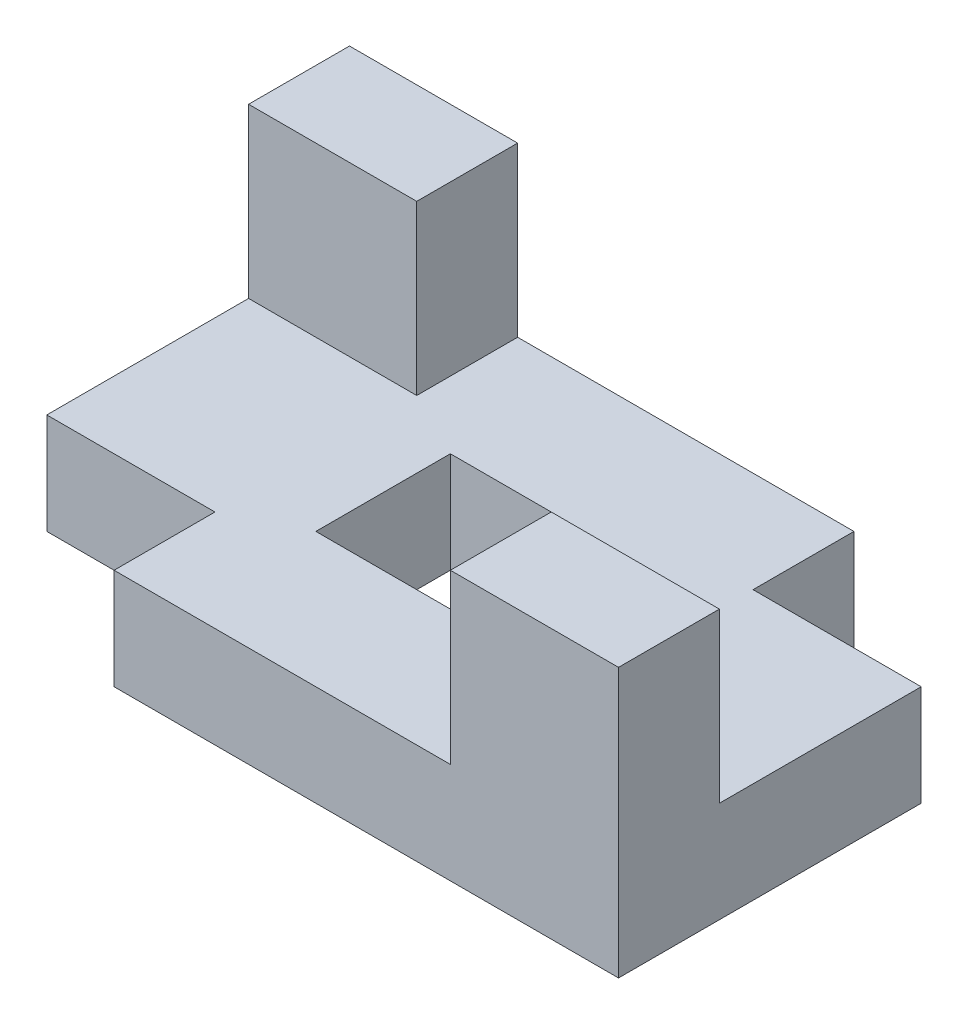
SolidWorks part; units mm, degrees
ref_plane "Front Plane" through (0, 0, 0) normal (0, 0, 1) x (1, 0, 0)
ref_plane "Top Plane" through (0, 0, 0) normal (0, 1, 0) x (1, 0, 0)
ref_plane "Right Plane" through (0, 0, 0) normal (1, 0, 0) x (0, 0, -1)
sketch "Sketch1" plane through (0, 0, 0) normal (0, 1, 0) x (1, 0, 0)
  line L1 (-50, -30) -> (50, -30)
  line L2 (-50, -30) -> (-50, 30)
  line L3 (-50, 30) -> (50, 30)
  line L4 (50, -30) -> (50, 30)
  line L5 (-50, -30) -> (50, 30) construction
  line L6 (-50, 30) -> (50, -30) construction
  line L7 (50, 30) -> (25, 30)
  line L8 (50, 30) -> (50, 15)
  line L9 (50, 15) -> (25, 15)
  line L10 (25, 30) -> (25, 15)
  line L11 (-50, -15) -> (-25, -15)
  line L12 (-50, -15) -> (-50, -30)
  line L13 (-50, -30) -> (-25, -30)
  line L14 (-25, -15) -> (-25, -30)
  line L15 (-50, 15) -> (-25, 15)
  line L16 (-50, 15) -> (-50, 30)
  line L17 (-50, 30) -> (-25, 30)
  line L18 (-25, 15) -> (-25, 30)
  line L19 (50, -15) -> (25, -15)
  line L20 (50, -15) -> (50, -30)
  line L21 (50, -30) -> (25, -30)
  line L22 (25, -15) -> (25, -30)
  line L23 (-15, -10) -> (15, -10)
  line L24 (-15, -10) -> (-15, 10)
  line L25 (-15, 10) -> (15, 10)
  line L26 (15, -10) -> (15, 10)
  line L27 (-15, -10) -> (15, 10) construction
  line L28 (-15, 10) -> (15, -10) construction
  point P0 (0, 0)
  point P20 (0, 0)
  point P25 (15, -6.4129)
  point P26 (15, -6.4129)
  dimension "D1" = 60
  dimension "D2" = 100
  dimension "D3" = 15
  dimension "D4" = 25
  dimension "D5" = 30
  dimension "D6" = 20
extrude "Boss-Extrude1" add sketch "Sketch1" along normal blind 15 contours L22 L19 L4 L9 L10 L3 L18 L15 L2 L11 L14 L1 L26 L23 L24 L25 region at (-23.8338, 0, 22.5)
extrude "Boss-Extrude2" add sketch "Sketch1<3>" along normal blind 40 contours L15 L18 L3 L2 | L19 L22 L1 L4 region at (37.5, 0, 22.5) region at (-37.5, 0, -22.5)
sketch "Sketch1<3>" plane through (0, 0, 0) normal (0, 1, 0) x (1, 0, 0) same geometry as "Sketch1"
